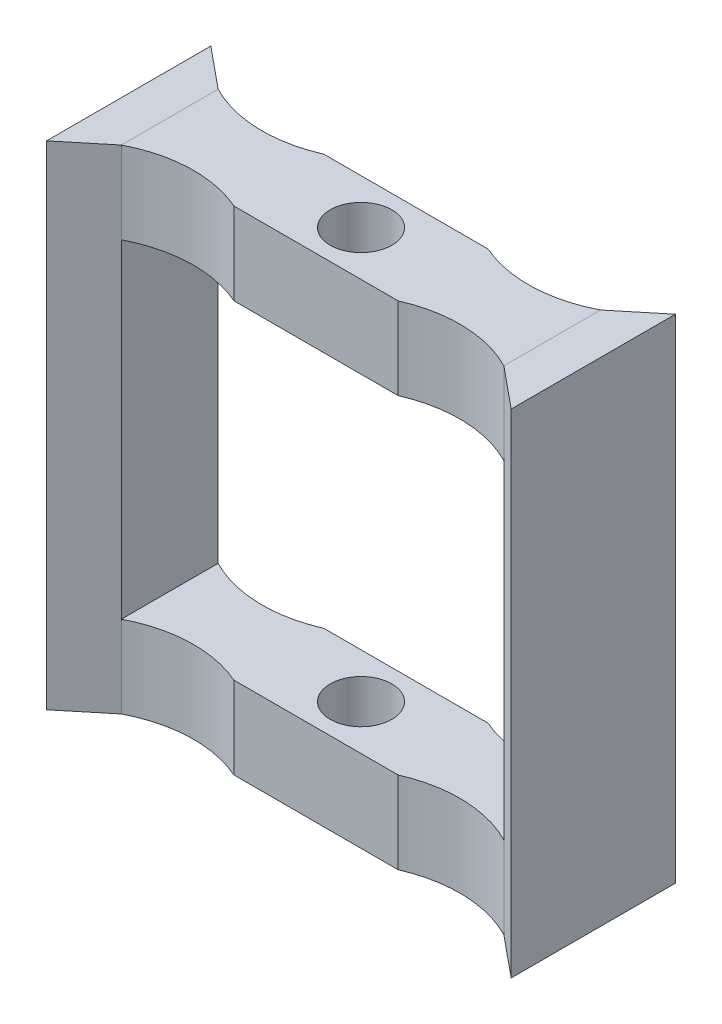
SolidWorks part; units mm, degrees
material "6061 Alloy"
ref_plane "Front Plane" through (0, 0, 0) normal (0, 0, 1) x (1, 0, 0)
ref_plane "Top Plane" through (0, 0, 0) normal (0, 1, 0) x (1, 0, 0)
ref_plane "Right Plane" through (0, 0, 0) normal (1, 0, 0) x (0, 0, -1)
sketch "Sketch1" plane through (0, 0, 0) normal (0, 1, 0) x (1, 0, 0)
  line L5 (-38.1, 0) -> (38.1, 0) construction
  line L7 (35.921, 12.7) -> (35.921, -12.7)
  line L8 (0, -12.7) -> (0, 12.7) construction
  line L13 (-35.921, 12.7) -> (-35.921, -12.7)
  line L14 (-8.0951, 9.7857) -> (0, 9.7857) construction
  line L15 (0, 9.7857) -> (8.0951, 9.7857) construction
  line L16 (-8.0951, -9.7857) -> (0, -9.7857) construction
  line L17 (0, -9.7857) -> (8.0951, -9.7857) construction
  line L18 (29.571, 7.4765) -> (29.571, -7.4765)
  line L19 (-29.571, 7.4765) -> (-29.571, -7.4765)
  line L20 (-12.7, 9.7857) -> (12.7, 9.7857) construction
  line L21 (-12.7, -9.7857) -> (12.7, -9.7857) construction
  line L22 (-12.7, 9.7857) -> (-12.7, -9.7857) construction
  line L23 (12.7, 9.7857) -> (12.7, -9.7857) construction
  line L30 (-12.7, 6.946) -> (12.7, 6.946)
  line L31 (-12.7, -6.946) -> (12.7, -6.946)
  line L32 (-29.571, 7.4765) -> (-12.7, 6.946)
  line L33 (-29.571, -7.4765) -> (-12.7, -6.946)
  line L34 (12.7, 6.946) -> (29.571, 7.4765)
  line L35 (12.7, -6.946) -> (29.571, -7.4765)
  circle A8 centre (0, 0) radius 38.1 construction
  circle A10 centre (0, 0) radius 12.7 construction
  arc A11 (8.0951, 9.7857) -> (35.921, 12.7) centre (20.58, 24.8779) ccw construction
  arc A12 (8.0951, -9.7857) -> (35.921, -12.7) centre (20.58, -24.8779) cw construction
  arc A13 (-8.0951, 9.7857) -> (-35.921, 12.7) centre (-20.58, 24.8779) cw construction
  arc A14 (-8.0951, -9.7857) -> (-35.921, -12.7) centre (-20.58, -24.8779) ccw construction
  arc A15 (-8.0951, 9.7857) -> (8.0951, 9.7857) centre (0, 0) cw construction
  arc A16 (-8.0951, -9.7857) -> (8.0951, -9.7857) centre (0, 0) ccw construction
  circle A17 centre (0, 0) radius 4.7625
  arc A18 (-29.571, 7.4765) -> (-8.0951, 9.7857) centre (-20.58, 24.8779) ccw construction
  arc A19 (-29.571, -7.4765) -> (-8.0951, -9.7857) centre (-20.58, -24.8779) cw construction
  arc A20 (8.0951, 9.7857) -> (29.571, 7.4765) centre (20.58, 24.8779) ccw construction
  arc A21 (8.0951, -9.7857) -> (29.571, -7.4765) centre (20.58, -24.8779) cw construction
  arc A22 (-29.571, 7.4765) -> (-12.7, 6.946) centre (-20.58, 24.8779) ccw construction
  arc A23 (-29.571, -7.4765) -> (-12.7, -6.946) centre (-20.58, -24.8779) cw construction
  arc A24 (29.571, 7.4765) -> (12.7, 6.946) centre (20.58, 24.8779) cw construction
  arc A25 (29.571, -7.4765) -> (12.7, -6.946) centre (20.58, -24.8779) ccw construction
  point P15 (22.6203, -5.3975)
  point P23 (22.6203, 5.3975)
  point P36 (0, 9.7857)
  dimension "D2" = 25.4
  dimension "D1" = 76.2
  dimension "D3" = 25.4
  dimension "D4" = 9.525
  dimension "D5" = 10.795
  dimension "D6" = 6.35
  dimension "D7" = 25.4
sketch "Sketch4" plane through (0, 0, 0) normal (0, 1, 0) x (1, 0, 0)
  line L0 (29.571, -7.4765) -> (35.921, -12.7)
  line L1 (35.921, -12.7) -> (35.921, 12.7)
  line L2 (35.921, 12.7) -> (29.571, 7.4765)
  line L3 (29.571, 7.4765) -> (29.571, -7.4765)
  line L4 (0, 9.7857) -> (0, -9.7857) construction
  line L5 (-35.921, 12.7) -> (-29.571, 7.4765)
  line L6 (-35.921, -12.7) -> (-35.921, 12.7)
  line L7 (-29.571, -7.4765) -> (-35.921, -12.7)
  line L8 (-29.571, 7.4765) -> (-29.571, -7.4765)
extrude "Boss-Extrude1" add sketch "Sketch4" along normal mid plane 76.2
sketch "Sketch5" plane through (0, 38.1, 0) normal (0, 1, 0) x (1, 0, 0)
  line L0 (-29.571, 7.4765) -> (-29.571, -7.4765) construction
  line L4 (29.571, 7.4765) -> (29.571, -7.4765) construction
  line L8 (-29.571, 7.4765) -> (-29.571, -7.4765)
  line L12 (29.571, 7.4765) -> (29.571, -7.4765)
  line L16 (-12.7, 6.946) -> (12.7, 6.946) construction
  line L17 (-12.7, -6.946) -> (12.7, -6.946) construction
  line L18 (-12.7, 6.946) -> (12.7, 6.946)
  line L19 (-12.7, -6.946) -> (12.7, -6.946)
  arc A0 (-29.571, 7.4765) -> (-12.7, 6.946) centre (-20.58, 24.8779) ccw construction
  arc A1 (12.7, 6.946) -> (29.571, 7.4765) centre (20.58, 24.8779) ccw construction
  arc A2 (29.571, -7.4765) -> (12.7, -6.946) centre (20.58, -24.8779) ccw construction
  arc A3 (-12.7, -6.946) -> (-29.571, -7.4765) centre (-20.58, -24.8779) ccw construction
  arc A4 (-29.571, 7.4765) -> (-12.7, 6.946) centre (-20.58, 24.8779) ccw
  arc A5 (12.7, 6.946) -> (29.571, 7.4765) centre (20.58, 24.8779) ccw
  arc A6 (29.571, -7.4765) -> (12.7, -6.946) centre (20.58, -24.8779) ccw
  arc A7 (-12.7, -6.946) -> (-29.571, -7.4765) centre (-20.58, -24.8779) ccw
  circle A8 centre (0, 0) radius 4.7625 construction
  circle A9 centre (0, 0) radius 4.7625
extrude "Boss-Extrude2" add sketch "Sketch5" against normal blind 12.7 separate body
mirror "Mirror2" about plane through (0, 0, 0) normal (0, 1, 0) of bodies 107
